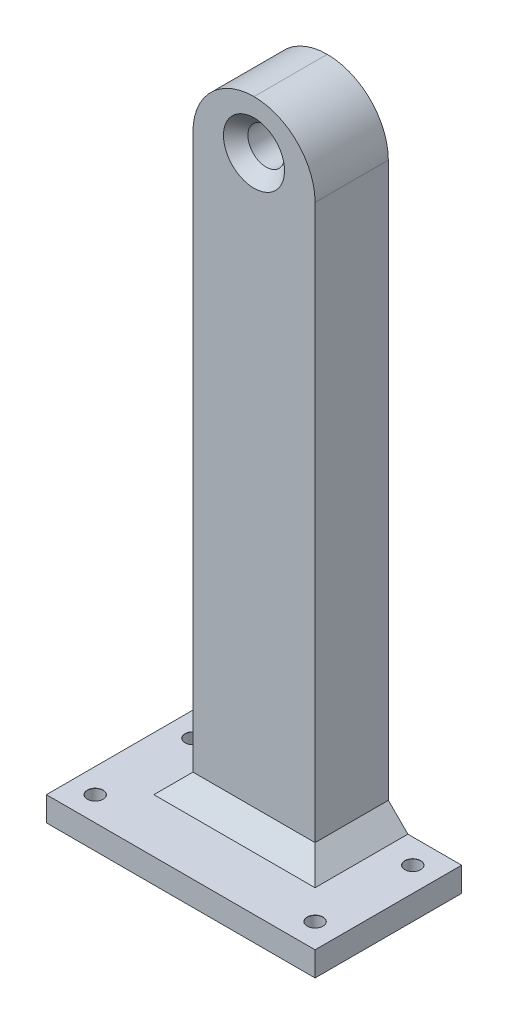
SolidWorks part; units mm, degrees
material "ABS"
ref_plane "Front Plane" through (0, 0, 0) normal (0, 0, 1) x (1, 0, 0)
ref_plane "Top Plane" through (0, 0, 0) normal (0, 1, 0) x (1, 0, 0)
ref_plane "Right Plane" through (0, 0, 0) normal (1, 0, 0) x (0, 0, -1)
sketch "Sketch1" plane through (0, 0, 0) normal (0, 0, 1) x (1, 0, 0)
  line L0 (0, 0) -> (-12.5, 0)
  line L1 (-12.5, 0) -> (-12.5, 135)
  line L3 (12.5, 135) -> (12.5, 0)
  line L4 (12.5, 0) -> (0, 0)
  line L5 (0, 0) -> (0, 125) construction
  line L8 (-12.5, 135) -> (12.5, 135)
  circle A1 centre (0, 125) radius 3.75
  dimension "D5" = 7.5
  dimension "D1" = 25
  dimension "D2" = 125
  dimension "D3" = 10
extrude "Boss-Extrude1" add sketch "Sketch1" along normal blind 15
sketch "Sketch2" plane through (0, 0, 0) normal (0, 0, -1) x (-1, 0, 0)
  line L0 (-27.5, 5) -> (27.5, 5)
  line L4 (-27.5, 0) -> (-27.5, 5)
  line L8 (27.5, 0) -> (27.5, 5)
  line L9 (27.5, 0) -> (-27.5, 0)
  line L10 (12.5, 135) -> (12.5, 0) construction
  point P0 (0, 0)
  dimension "D1" = 15
  dimension "D2" = 5
extrude "Boss-Extrude2" add sketch "Sketch2" against normal blind 30
sketch "Sketch5" plane through (0, 5, 0) normal (0, 1, 0) x (1, 0, 0)
  line L0 (-27.5, 0) -> (-12.5, 0) construction
  line L1 (-27.5, -30) -> (27.5, -30) construction
  line L2 (-27.5, -30) -> (-27.5, 0) construction
  line L3 (27.5, -30) -> (27.5, 0) construction
  point P0 (-22.5, -5)
  point P2 (-22.5, -25)
  point P4 (22.5, -25)
  point P6 (22.5, -5)
  dimension "D1" = 5
  dimension "D2" = 5
  dimension "D3" = 5
  dimension "D4" = 5
hole_wizard "Ø3.2 (3.2) Diameter Hole1" positions "Sketch5" profile "Sketch4" hole size "Ø3.2" standard "ANSI Metric" end condition through all
sketch "Sketch4" plane through (-22.5, 5, 5) normal (1, 0, 0) x (0, 0, 1)
  line L0 (0, 0) -> (0, 5)
  line L1 (0, 5) -> (1.6, 5)
  line L2 (1.6, 5) -> (1.6, 0.025)
  line L3 (1.6, 0.025) -> (1.625, 0)
  line L5 (1.625, 0) -> (0, 0)
  line L6 (-1.6, 0.025) -> (-1.625, 0) construction
  line L11 (0, -6.35) -> (0, 107.95) construction
  dimension "Thru Hole Dia." = 3.2
  dimension "Thru Hole Depth" = 5
  dimension "Near C'Sink Dia." = 3.25
  dimension "Near C'Sink Angle" = 90
chamfer "Chamfer1" distance 4 angle 45 3 edges at (12.5, 5, 7.5) (-12.5, 5, 7.5) (0, 5, 15)
fillet "Fillet2" radius 12.5 2 edges at (12.5, 135, 7.5) (-12.5, 135, 7.5)
chamfer "Chamfer2" distance 2.5 angle 45 1 edges at (3.75, 125, 15)
